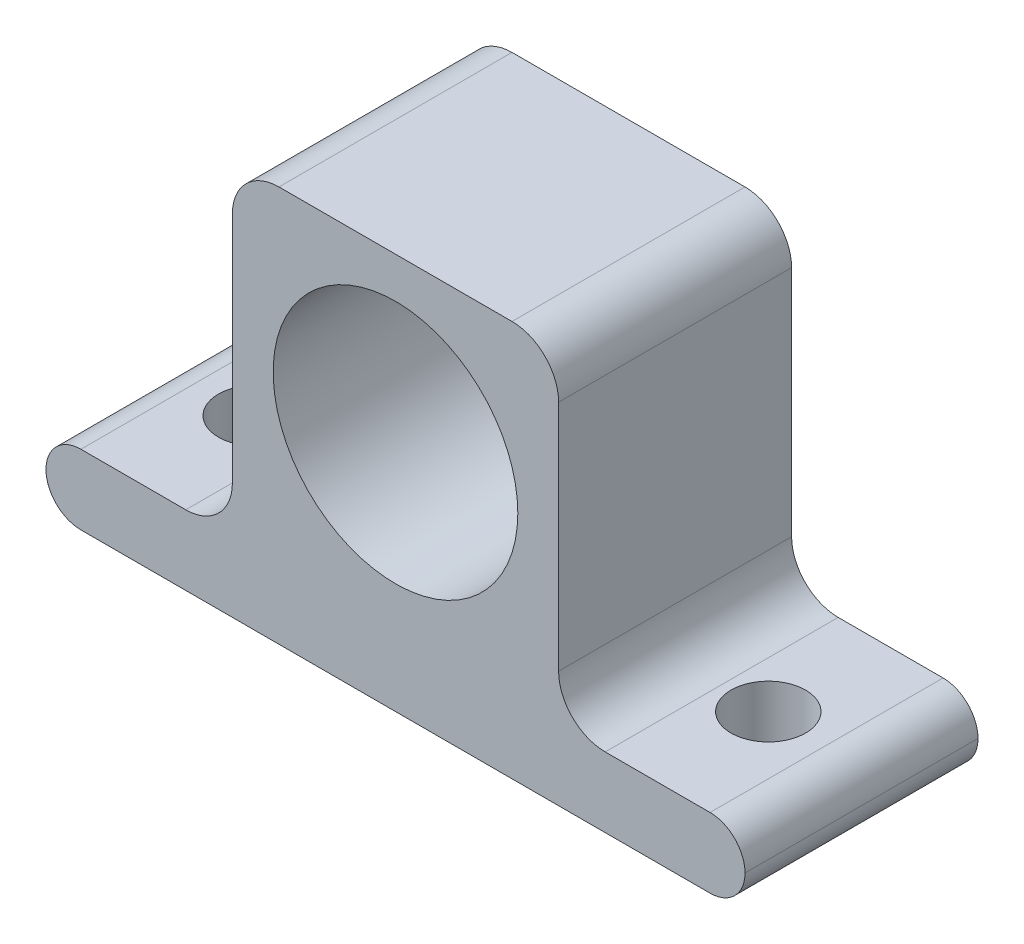
SolidWorks part; units mm, degrees
ref_plane "Front Plane" through (0, 0, 0) normal (0, 0, 1) x (1, 0, 0)
ref_plane "Top Plane" through (0, 0, 0) normal (0, 1, 0) x (1, 0, 0)
ref_plane "Right Plane" through (0, 0, 0) normal (1, 0, 0) x (0, 0, -1)
sketch "Sketch1" plane through (0, 0, 0) normal (0, 0, 1) x (1, 0, 0)
  line L0 (-15, 0) -> (15, 0)
  line L1 (15, 0) -> (15, 3)
  line L2 (15, 3) -> (7, 3)
  line L3 (7, 3) -> (7, 17)
  line L4 (7, 17) -> (-7, 17)
  line L5 (-7, 17) -> (-7, 3)
  line L6 (-7, 3) -> (-15, 3)
  line L7 (-15, 3) -> (-15, 0)
  point P4 (0, 0)
  dimension "D1" = 14
  dimension "D2" = 3
  dimension "D3" = 14
  dimension "D4" = 30
extrude "Boss-Extrude1" add sketch "Sketch1" along normal mid plane 10
sketch "Sketch2" plane through (0, 0, 5) normal (0, 0, 1) x (1, 0, 0)
  line L0 (7, 17) -> (-7, 17) construction
  line L1 (-7, 17) -> (-7, 3) construction
  circle A0 centre (0, 10) radius 5.25
  point P5 (0, 17)
  point P9 (-7, 10)
  dimension "D1" = 10.5
extrude "Cut-Extrude1" cut sketch "Sketch2" against normal through all
sketch "Sketch3" plane through (0, 3, 0) normal (0, 1, 0) x (1, 0, 0)
  line L0 (15, -5) -> (15, 5) construction
  line L1 (-15, -5) -> (-15, 5) construction
  line L2 (-7, -5) -> (-15, -5) construction
  line L3 (15, -5) -> (7, -5) construction
  circle A0 centre (11, 0) radius 1.6
  circle A1 centre (-11, 0) radius 1.6
  point P7 (15, 0)
  point P11 (-15, 0)
  point P15 (-11, -5)
  point P19 (11, -5)
  dimension "D1" = 3.2
extrude "Cut-Extrude2" cut sketch "Sketch3" against normal through all
fillet "Fillet1" radius 2 4 edges at (7, 17, 0) (-7, 17, 0) (-7, 3, 0) (7, 3, 0)
fillet "Fillet2" radius 1.5 4 edges at (-15, 0, 0) (-15, 3, 0) (15, 3, 0) (15, 0, 0)
